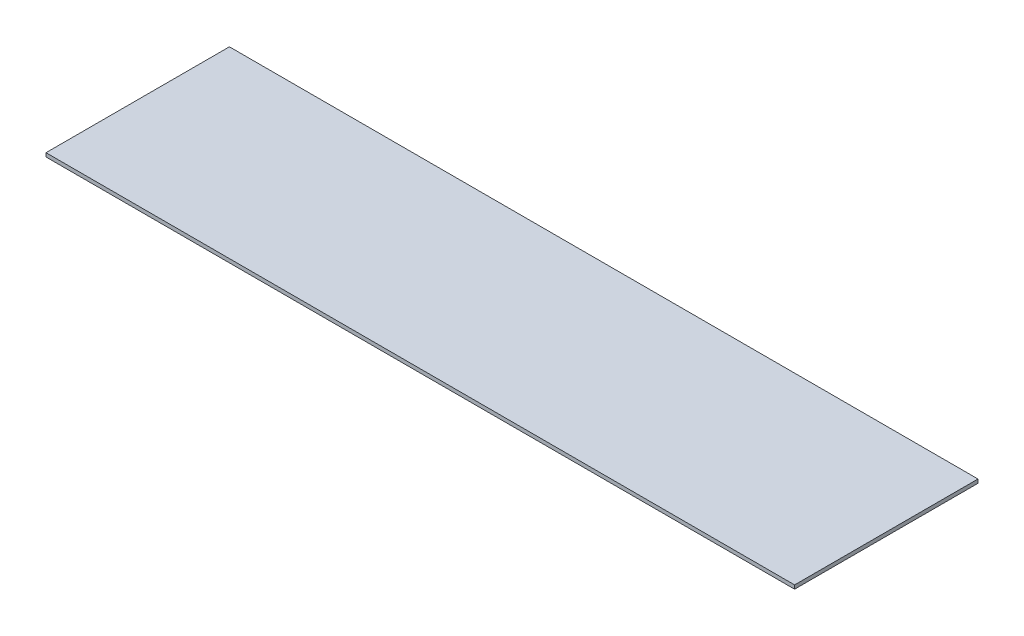
SolidWorks part; units mm, degrees
ref_plane "Ebene vorne" through (0, 0, 0) normal (0, 0, 1) x (1, 0, 0)
ref_plane "Ebene oben" through (0, 0, 0) normal (0, 1, 0) x (1, 0, 0)
ref_plane "Ebene rechts" through (0, 0, 0) normal (1, 0, 0) x (0, 0, -1)
sketch "Sketch1" plane through (0, 0, 0) normal (1, 0, 0) x (0, 0, -1)
  line L0 (0, 0) -> (0, 2)
  line L1 (0, 0) -> (98, 0)
  line L2 (98, 0) -> (98, 2)
  line L5 (0, 2) -> (98, 2)
  dimension "D4" = 2
  dimension "D5" = 98
extrude "Boss-Extrude1" add sketch "Sketch1" along normal blind 400
